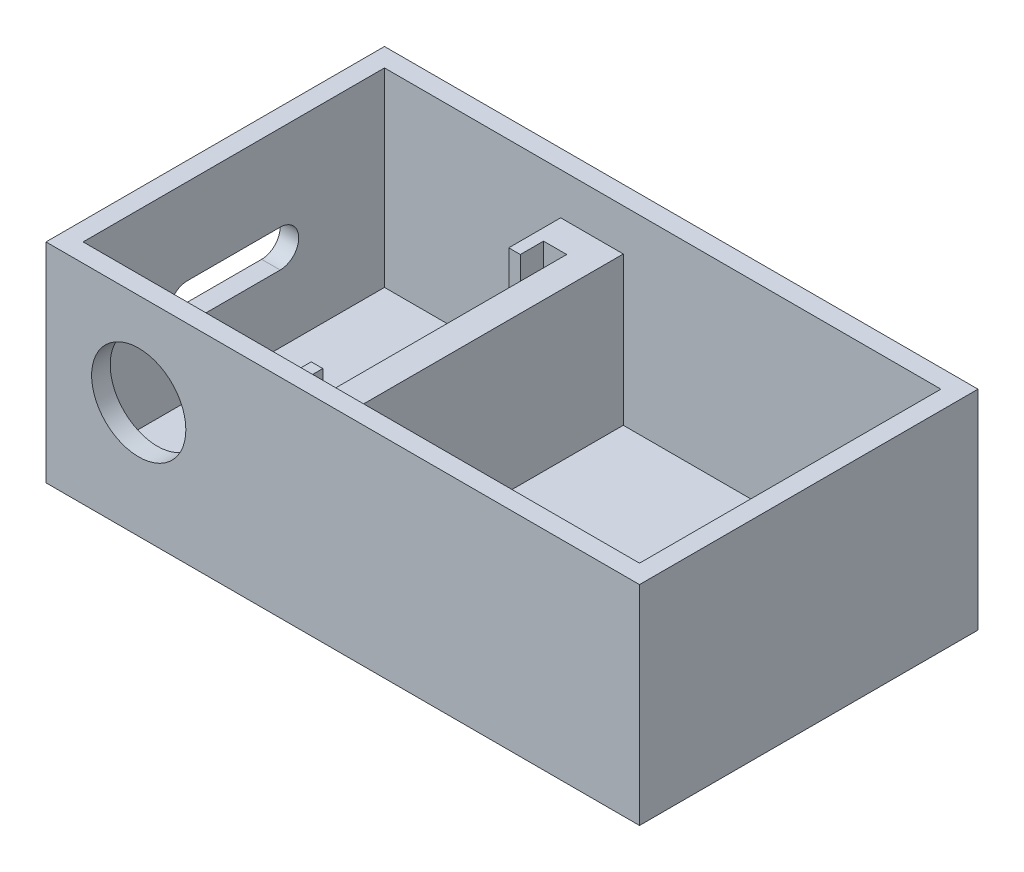
SolidWorks part; units mm, degrees
material "ABS"
ref_plane "Front Plane" through (0, 0, 0) normal (0, 0, 1) x (1, 0, 0)
ref_plane "Top Plane" through (0, 0, 0) normal (0, 1, 0) x (1, 0, 0)
ref_plane "Right Plane" through (0, 0, 0) normal (1, 0, 0) x (0, 0, -1)
sketch "Sketch1" plane through (0, 0, 0) normal (0, 1, 0) x (1, 0, 0)
  line L0 (64, 36.5) -> (-64, 36.5)
  line L1 (60, 32.5) -> (-60, 32.5)
  line L2 (60, 32.5) -> (60, -32.5)
  line L3 (60, -32.5) -> (-60, -32.5)
  line L4 (-60, 32.5) -> (-60, -32.5)
  line L5 (60, 32.5) -> (-60, -32.5) construction
  line L6 (60, -32.5) -> (-60, 32.5) construction
  line L7 (-64, 36.5) -> (-64, -36.5)
  line L8 (64, -36.5) -> (-64, -36.5)
  line L9 (64, 36.5) -> (64, -36.5)
  point P0 (0, 0)
  dimension "D1" = 120
  dimension "D2" = 65
  dimension "D3" = 4
extrude "Boss-Extrude1" add sketch "Sketch1" along normal blind 41 contours L1 L4 L3 L2 | L0 L7 L8 L9 region at (0, 0, 0)
extrude "Boss-Extrude2" add sketch "Sketch1<3>" against normal blind 4 contours L0 L7 L8 L9
sketch "Sketch1<3>" plane through (0, 0, 0) normal (0, 1, 0) x (1, 0, 0) same geometry as "Sketch1"
sketch "Sketch3" plane through (0, 0, 36.5) normal (0, 0, 1) x (1, 0, 0)
  line L0 (-64, 41) -> (-64, -4) construction
  line L1 (64, -4) -> (-64, -4) construction
  circle A0 centre (-44, 21) radius 10.16
  dimension "D1" = 20.32
  dimension "D2" = 20
  dimension "D3" = 25
extrude "Cut-Extrude1" cut sketch "Sketch3" against normal blind 4
sketch "Sketch4" plane through (-64, 0, 0) normal (-1, 0, 0) x (0, 0, 1)
  line L0 (-36.5, -4) -> (36.5, 41) construction
  line L1 (36.5, -4) -> (-36.5, 41) construction
  line L2 (10, 18.5) -> (-10, 18.5) construction
  line L3 (10, 14.5) -> (-10, 14.5)
  line L4 (10, 22.5) -> (-10, 22.5)
  arc A1 (10, 14.5) -> (10, 22.5) centre (10, 18.5) ccw
  arc A2 (-10, 22.5) -> (-10, 14.5) centre (-10, 18.5) ccw
  point P8 (0, 18.5)
  point P11 (0, 18.5)
  dimension "D1" = 20
  dimension "D2" = 8
sketch "Sketch5" plane through (0, 0, 0) normal (0, 1, 0) x (1, 0, 0)
  line L0 (60, 32.5) -> (-60, 32.5) construction
  line L1 (-14.5, 32.5) -> (-8.5, 32.5)
  line L2 (-14.5, 32.5) -> (-14.5, -32.5)
  line L3 (-14.5, -32.5) -> (-8.5, -32.5)
  line L4 (-8.5, 32.5) -> (-8.5, -32.5)
  line L5 (60, -32.5) -> (-60, -32.5) construction
  line L6 (60, 32.5) -> (60, -32.5) construction
  dimension "D1" = 6
  dimension "D2" = 74.5
extrude "Boss-Extrude3" add sketch "Sketch5" along normal blind 32 contours L2 L3 L4 L1
sketch "Sketch8" plane through (0, 0, 0) normal (0, 1, 0) x (1, 0, 0)
  line L0 (0, 0) -> (-36.4033, 0) construction
  line L1 (-14.5, 32.5) -> (-22, 32.5)
  line L2 (-14.5, 32.5) -> (-14.5, -32.5) construction
  line L3 (-22, 32.5) -> (-22, 21.3)
  line L4 (-22, 21.3) -> (-19.5, 21.3)
  line L5 (-19.5, 21.3) -> (-19.5, 26.3)
  line L6 (-19.5, 26.3) -> (-14.5, 26.3)
  line L7 (-14.5, 26.3) -> (-14.5, 32.5)
  line L9 (60, 32.5) -> (-60, 32.5) construction
  line L10 (-14.5, -26.3) -> (-14.5, -32.5)
  line L11 (-19.5, -26.3) -> (-14.5, -26.3)
  line L12 (-19.5, -21.3) -> (-19.5, -26.3)
  line L13 (-22, -21.3) -> (-19.5, -21.3)
  line L14 (-22, -32.5) -> (-22, -21.3)
  line L15 (-14.5, -32.5) -> (-22, -32.5)
  dimension "D1" = 6.2
  dimension "D2" = 5
  dimension "D3" = 2.5
  dimension "D4" = 5
extrude "Boss-Extrude4" add sketch "Sketch8" along normal blind 32 contours L3 L4 L5 L6 L7 L1 | L14 L13 L12 L11 L10 L15
extrude "Cut-Extrude2" cut sketch "Sketch4" against normal blind 10 contours L4 A2 L3 A1
